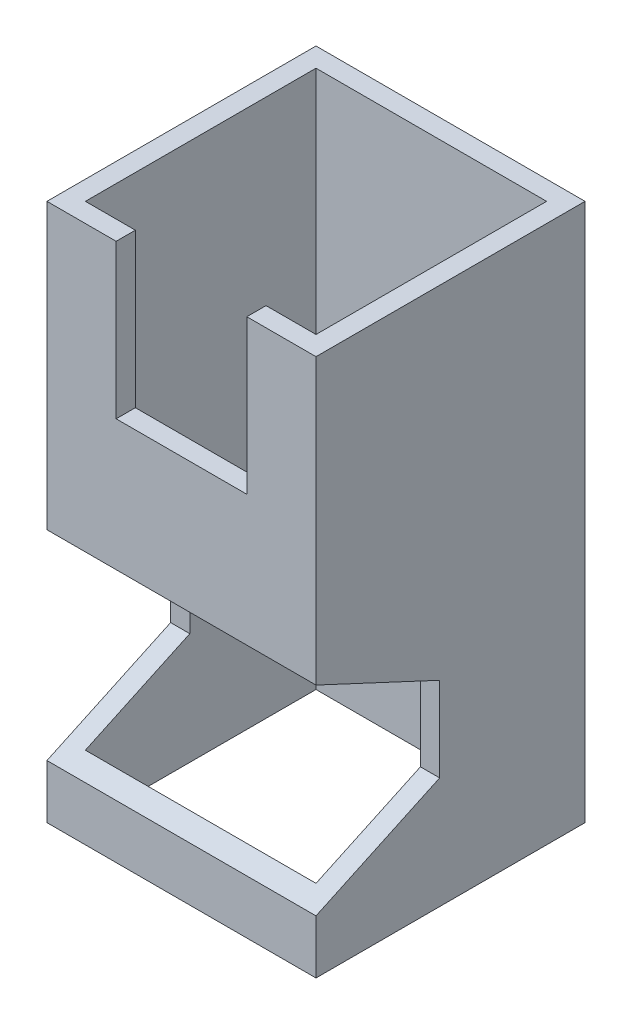
SolidWorks part; units mm, degrees
ref_plane "Front Plane" through (0, 0, 0) normal (0, 0, 1) x (1, 0, 0)
ref_plane "Top Plane" through (0, 0, 0) normal (0, 1, 0) x (1, 0, 0)
ref_plane "Right Plane" through (0, 0, 0) normal (1, 0, 0) x (0, 0, -1)
sketch "Sketch1" plane through (0, 0, 0) normal (0, 1, 0) x (1, 0, 0)
  line L1 (0, 0) -> (30, 0)
  line L2 (0, 0) -> (0, 30)
  line L3 (0, 30) -> (30, 30)
  line L4 (30, 0) -> (30, 30)
  line L5 (0, 0) -> (30, 30) construction
  line L6 (0, 30) -> (30, 0) construction
  line L7 (-2.5, 32.5) -> (32.5, 32.5)
  line L8 (-2.5, 32.5) -> (-2.5, -2.5)
  line L9 (-2.5, -2.5) -> (32.5, -2.5)
  line L10 (32.5, 32.5) -> (32.5, -2.5)
  line L11 (-2.5, 32.5) -> (32.5, -2.5) construction
  line L12 (-2.5, -2.5) -> (32.5, 32.5) construction
  point P4 (15, 15)
  point P10 (15, 15)
  point P11 (3.2794, 3.2794)
  point P12 (-1.6471, -2.5)
  dimension "D1" = 2.5
  dimension "D2" = 30
extrude "Boss-Extrude1" add sketch "Sketch1" along normal blind 70
sketch "Sketch2" plane through (0, 0, 2.5) normal (0, 0, 1) x (1, 0, 0)
  line L0 (-2.5, 70) -> (32.5, 70) construction
  line L1 (6.5, 70) -> (23.5, 70)
  line L2 (6.5, 70) -> (6.5, 50)
  line L3 (6.5, 50) -> (23.5, 50)
  line L4 (23.5, 70) -> (23.5, 50)
  line L5 (6.5, 70) -> (23.5, 50) construction
  line L6 (6.5, 50) -> (23.5, 70) construction
  line L7 (15, 0) -> (15, 60) construction
  line L8 (-2.5, 0) -> (32.5, 0) construction
  line L9 (15, 60) -> (15, 70) construction
  point P4 (15, 60)
  dimension "D1" = 20
  dimension "D2" = 17
extrude "Cut-Extrude1" cut sketch "Sketch2" against normal up to surface (2.5 mm away) up to face at (15, 35, 0)
sketch "Sketch3" plane through (-2.5, 0, 0) normal (-1, 0, 0) x (0, 0, 1)
  line L0 (2.5, 33) -> (-13.5838, 25.5)
  line L1 (2.5, 70) -> (2.5, 0) construction
  line L2 (-13.5838, 25.5) -> (-13.5838, 14.5)
  line L3 (-13.5838, 14.5) -> (2.5, 7)
  line L4 (2.5, 7) -> (2.5, 33)
  line L5 (-13.5838, 20) -> (2.5, 20) construction
  line L6 (-13.5838, 14.5) -> (-25.3786, 20) construction
  line L7 (-25.3786, 20) -> (-13.5838, 25.5) construction
  line L8 (-32.5, 0) -> (2.5, 0) construction
  dimension "D1" = 50
  dimension "D2" = 26
  dimension "D3" = 11
  dimension "D4" = 20
extrude "Cut-Extrude2" cut sketch "Sketch3" against normal through all
